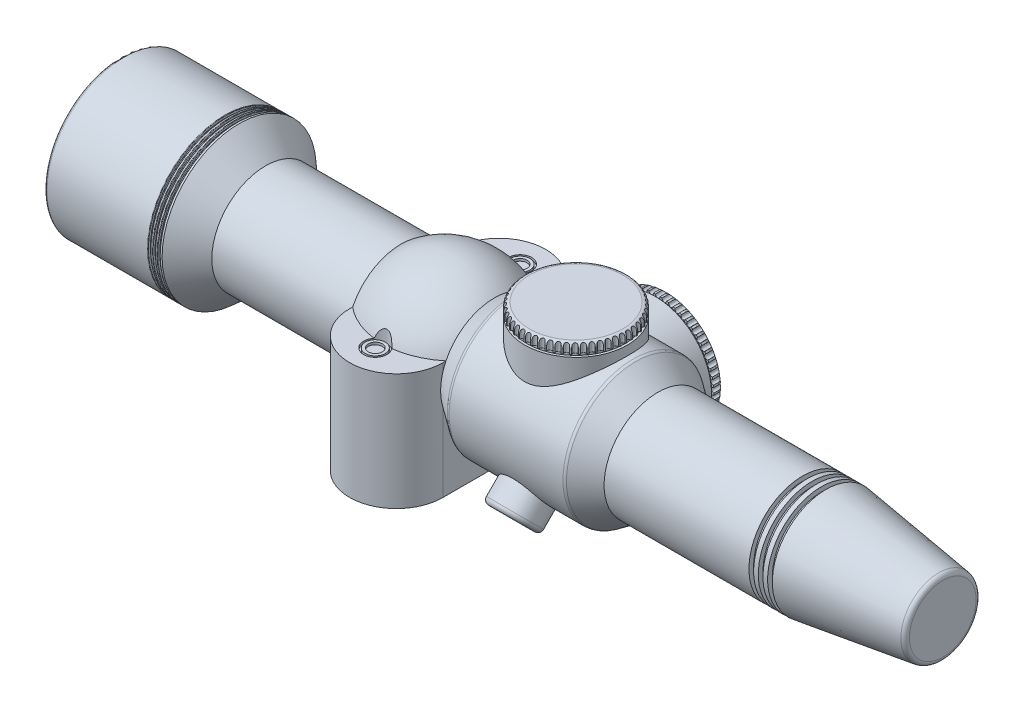
SolidWorks part; units mm, degrees
ref_plane "Front Plane" through (0, 0, 0) normal (0, 0, 1) x (1, 0, 0)
ref_plane "Top Plane" through (0, 0, 0) normal (0, 1, 0) x (1, 0, 0)
ref_plane "Right Plane" through (0, 0, 0) normal (1, 0, 0) x (0, 0, -1)
sketch "Sketch1" plane through (0, 0, 0) normal (1, 0, 0) x (0, 0, -1)
  circle A0 centre (0, 0) radius 16.5
  dimension "D1" = 33
extrude "Boss-Extrude1" add sketch "Sketch1" along normal blind 25.15
sketch "Sketch2" plane through (0, 0, 0) normal (-1, 0, 0) x (0, 0, 1)
  circle A0 centre (0, 0) radius 14.125
  dimension "D1" = 28.25
extrude "Cut-Extrude1" cut sketch "Sketch2" against normal blind 1
sketch "Sketch3" plane through (1, 0, 0) normal (-1, 0, 0) x (0, 0, 1)
  circle A0 centre (0, 0) radius 13.125
  dimension "D1" = 26.25
ref_plane "Plane1" through (25.15, 0, 0) normal (0, -1, 0) x (0, 0, 1)
extrude "Cut-Extrude6" cut sketch "Sketch3" against normal blind 1 contours A0
sketch "Sketch14" plane through (2, 0, 0) normal (-1, 0, 0) x (0, 0, 1)
  circle A0 centre (0, 0) radius 12.125
  dimension "D1" = 24.25
extrude "Cut-Extrude7" cut sketch "Sketch14" against normal blind 1
sketch "Sketch15" plane through (3, 0, 0) normal (-1, 0, 0) x (0, 0, 1)
  circle A0 centre (0, 0) radius 11.125
  dimension "D1" = 22.25
extrude "Cut-Extrude8" cut sketch "Sketch15" against normal blind 1
sketch "Sketch16" plane through (4, 0, 0) normal (-1, 0, 0) x (0, 0, 1)
  circle A0 centre (0, 0) radius 10.125
  dimension "D1" = 20.25
extrude "Cut-Extrude9" cut sketch "Sketch16" against normal blind 1
sketch "Sketch17" plane through (5, 0, 0) normal (-1, 0, 0) x (0, 0, 1)
  circle A0 centre (0, 0) radius 9.125
  dimension "D1" = 18.25
extrude "Cut-Extrude10" cut sketch "Sketch17" against normal blind 3
sketch "Sketch18" plane through (0, 0, 0) normal (0, 1, 0) x (1, 0, 0)
  line L0 (25.15, 0) -> (0, 0) construction
  line L1 (6.4671, 0) -> (8, 0)
  line L2 (8, 9.125) -> (8, -9.125) construction
  line L3 (8, 0) -> (8, 9.125)
  spline S0 degree 2 poles (8, 9.125) (6.4671, 4.5625) (6.4671, 0) knots 0 0 0 0.5 0.5 0.5
revolve "Revolve1" add sketch "Sketch18" angle 360 about axis through (25.15, 0, 0) along (-1, 0, 0)
sketch "Sketch20" plane through (0, 0, 0) normal (0, 1, 0) x (1, 0, 0)
  line L0 (25.15, 0) -> (30.8, 0)
  line L1 (25.15, -16.5) -> (25.15, 16.5) construction
  line L2 (25.15, 0) -> (0, 0) construction
  line L3 (30.8, 0) -> (30.8, 11.5)
  line L4 (30.8, 11.5) -> (25.15, 16.5)
  line L5 (25.15, 16.5) -> (25.15, 0)
  line L6 (25.15, 0) -> (25.0816, -0.0545)
  dimension "D1" = 11.5
  dimension "D2" = 5.65
revolve "Revolve5" add sketch "Sketch20" angle 360 about L0 region at (27.8068, 0, -7.0744)
sketch "Sketch21" plane through (30.8, 0, 0) normal (1, 0, 0) x (0, 0, -1)
  circle A0 centre (0, 0) radius 11.5
extrude "Shaft" add sketch "Sketch21" along normal blind 120
sketch "Sketch25" plane through (0, 0, 0) normal (0, 1, 0) x (1, 0, 0)
  line L0 (23.15, 16.5) -> (23.65, 16.5)
  line L1 (25.15, 16.5) -> (0, 16.5) construction
  line L2 (24.65, 16.5) -> (24.65, 16)
  line L3 (24.65, 16) -> (24.15, 16)
  line L4 (24.15, 16) -> (24.15, 16.5)
  line L5 (25.15, 16.5) -> (0, 16.5) construction
  line L7 (25.15, 16.5) -> (0, 16.5) construction
  line L8 (23.65, 16.5) -> (23.65, 16)
  line L9 (23.65, 16) -> (23.15, 16)
  line L10 (23.15, 16) -> (23.15, 16.5)
  line L11 (25.15, 16.5) -> (0, 16.5) construction
  line L12 (24.15, 16.5) -> (24.65, 16.5)
  line L13 (25.15, 16.5) -> (0, 16.5) construction
  line L14 (22.65, 16.5) -> (22.65, 16)
  line L15 (22.65, 16) -> (22.15, 16)
  line L16 (22.15, 16) -> (22.15, 16.5)
  line L17 (25.15, 16.5) -> (0, 16.5) construction
  line L18 (22.15, 16.5) -> (22.65, 16.5)
  line L20 (23.65, 16.5) -> (23.6371, 16.4877)
  dimension "D1" = 0.5
  dimension "D2" = 0.5
  dimension "D3" = 0.5
  dimension "D4" = 0.5
  dimension "D5" = 0.5
  dimension "D6" = 0.5
  dimension "D8" = 0.5
  dimension "D9" = 0.5
revolve "Cut-Revolve13" cut sketch "Sketch25" angle 360 about axis through (25.15, 0, 0) along (-1, 0, 0)
fillet "Fillet1" radius 0.1 6 edges at (24.65, 0, -16.5) (24.15, 0, -16.5) (23.65, 0, -16.5) (23.15, 0, -16.5) (22.65, 0, -16.5) (22.15, 0, -16.5)
fillet "Fillet2" radius 0.5 1 edges at (0, 0, -16.5)
sketch "Sketch26" plane through (0, 0, 0) normal (0, 1, 0) x (1, 0, 0)
  line L0 (150.8, -11.5) -> (150.8, 0)
  line L1 (150.8, -11.5) -> (150.8, 11.5) construction
  line L2 (150.8, 0) -> (175.8, 0)
  line L3 (150.8, 0) -> (30.8, 0) construction
  line L4 (175.8, 0) -> (175.8, -7.1302)
  line L5 (174.9386, -8.1206) -> (150.8, -11.5)
  arc A0 (175.8, -7.1302) -> (174.9386, -8.1206) centre (174.8, -7.1302) cw
  point P12 (175.8, -8)
  dimension "D3" = 1
  dimension "D1" = 25
  dimension "D2" = 8
revolve "Revolve6" add sketch "Sketch26" angle 360 about axis through (150.8, 0, 0) along (-1, 0, 0)
sketch "Sketch27" plane through (0, 0, 0) normal (0, 1, 0) x (1, 0, 0)
  line L0 (147.8, -11.5) -> (147.8, -10.5)
  line L1 (150.8, -11.5) -> (149.8, -11.5)
  line L2 (150.8, -11.5) -> (150.8, -10.5)
  line L3 (150.8, -10.5) -> (149.8, -10.5)
  line L4 (149.8, -11.5) -> (149.8, -10.5)
  line L5 (148.8, -11.5) -> (147.8, -11.5)
  line L6 (148.8, -11.5) -> (148.8, -10.5)
  line L7 (148.8, -10.5) -> (147.8, -10.5)
  line L8 (145.8, -11.5) -> (145.8, -10.5)
  line L9 (146.8, -11.5) -> (145.8, -11.5)
  line L10 (146.8, -11.5) -> (146.8, -10.5)
  line L11 (146.8, -10.5) -> (145.8, -10.5)
  dimension "D1" = 1
  dimension "D2" = 1
  dimension "D3" = 3
revolve "Cut-Revolve14" cut sketch "Sketch27" angle 360 about axis through (150.8, 0, 0) along (-1, 0, 0)
sketch "Sketch28" plane through (0, 0, 0) normal (0, 1, 0) x (1, 0, 0)
  line L0 (145.8, 0) -> (30.8, 0) construction
  line L1 (59.8, 11) -> (59.8, -11)
  line L2 (79.8, -11) -> (79.8, 11)
  line L3 (30.8, 11.5) -> (30.8, -11.5) construction
  arc A0 (79.8, 11) -> (59.8, 11) centre (69.8, 11) ccw
  arc A1 (59.8, -11) -> (79.8, -11) centre (69.8, -11) ccw
  dimension "D1" = 20
  dimension "D2" = 20
  dimension "D3" = 22
  dimension "D4" = 11
  dimension "D5" = 29
extrude "Boss-Extrude2" add sketch "Sketch28" against normal blind 20 and the other way blind 5
sketch "Sketch29" plane through (0, -20, 0) normal (0, -1, 0) x (1, 0, 0)
  circle A0 centre (69.8, -11) radius 2.75
  circle A1 centre (69.8, 7) radius 2.75
  dimension "D1" = 5.5
  dimension "D3" = 5.5
  dimension "D2" = 18
extrude "Cut-Extrude11" cut sketch "Sketch29" against normal blind 10
sketch "Sketch30" plane through (0, 0, 0) normal (0, 1, 0) x (1, 0, 0)
  line L0 (69.8, 14.8562) -> (54.6498, 14.8562) construction
  line L2 (59.8125, 11.5) -> (79.7875, 11.5)
  arc A0 (59.8125, 11.5) -> (79.7875, 11.5) centre (69.8, -1.6827) cw
revolve "Revolve7" add sketch "Sketch30" angle 180 about axis through (150.8, 0, 0) along (-1, 0, 0) reverse direction yes
sketch "Sketch31" plane through (0, 5, 0) normal (0, 1, 0) x (1, 0, 0)
  circle A0 centre (69.8, 15.5) radius 2.5
  arc A1 (79.8, 11) -> (59.8, 11) centre (69.8, 11) ccw construction
  point P2 (69.8, 21)
  dimension "D1" = 5
  dimension "D2" = 5.5
extrude "Cut-Extrude12" cut sketch "Sketch31" against normal blind 0.5 and the other way blind 10
sketch "Sketch32" plane through (0, 4.5, 0) normal (0, 1, 0) x (1, 0, 0)
  circle A0 centre (69.8, 15.5) radius 2.125
  circle A1 centre (69.8, 15.5) radius 1.5
  dimension "D1" = 4.25
  dimension "D2" = 3
extrude "Boss-Extrude3" add sketch "Sketch32" along normal blind 0.5
mirror "Mirror2" about plane through (0, 0, 0) normal (0, 0, 1) of "Boss-Extrude3", "Cut-Extrude12"
sketch "Sketch33" plane through (0, 0, 0) normal (0, 1, 0) x (1, 0, 0)
  line L0 (79.7875, 11.5) -> (84.5293, 14.8192)
  line L1 (85.1027, 15) -> (109.4723, 15)
  line L2 (110.0457, 14.8192) -> (114.7875, 11.5)
  line L3 (145.8, 11.5) -> (79.7875, 11.5) construction
  line L4 (114.7875, 11.5) -> (79.7875, 11.5)
  line L5 (145.8, 0) -> (79.7875, 0) construction
  arc A0 (110.0457, 14.8192) -> (109.4723, 15) centre (109.4723, 14) ccw
  arc A1 (85.1027, 15) -> (84.5293, 14.8192) centre (85.1027, 14) ccw
  point P11 (109.7875, 15)
  point P14 (84.7875, 15)
  dimension "D5" = 1
  dimension "D1" = 5
  dimension "D2" = 5
  dimension "D3" = 25
  dimension "D4" = 15
revolve "Revolve8" add sketch "Sketch33" angle 360 about axis through (150.8, 0, 0) along (-1, 0, 0)
sketch "Sketch34" plane through (0, 0, 0) normal (0, 0, 1) x (1, 0, 0)
  line L0 (85.1027, 0) -> (109.4723, 0) construction
  line L1 (114.7875, 11.5) -> (114.7875, -11.5) construction
  circle A0 centre (97.2875, 0) radius 12
  dimension "D2" = 24
  dimension "D1" = 17.5
extrude "Boss-Extrude4" add sketch "Sketch34" against normal blind 19.5
fillet "Fillet3" radius 1 1 edges at (109.2875, 0, -19.5)
sketch "Sketch36" plane through (0, 0, 0) normal (0, 1, 0) x (1, 0, 0)
  line L1 (85.2875, 18.5) -> (85.2875, 15) construction
  line L2 (85.2875, 17.5) -> (85.7875, 17.5)
  line L3 (85.2875, 17.5) -> (85.2875, 17)
  line L4 (85.2875, 17) -> (85.7875, 17)
  line L6 (85.7875, 17.5) -> (85.7875, 17)
  line L7 (109.2875, 18.5) -> (85.2875, 18.5) construction
  dimension "D1" = 0.5
  dimension "D2" = 0.5
  dimension "D3" = 1
revolve "Cut-Revolve15" cut sketch "Sketch36" angle 360 about axis through (97.2875, 0, -19.5) along (0, 0, 1)
sketch "Sketch38" plane through (0, 0, -19.5) normal (0, 0, -1) x (-1, 0, 0)
  line L0 (-97.2875, 0) -> (-97.2875, 15.7443) construction
sketch "Sketch39" plane through (0, 0, -19.5) normal (0, 0, -1) x (-1, 0, 0)
  line L0 (-97.2875, 0) -> (-97.2875, 15.7443) construction
  circle A0 centre (-97.2875, 12) radius 0.5
  circle A1 centre (-97.2875, 0) radius 12 construction
  dimension "D1" = 1
extrude "Cut-Extrude13" cut sketch "Sketch39" against normal up to next
pattern_circular "CirPattern1" count 53 over 360 about axis through (97.2875, 0, -18.5) along (0, 0, 1) of "Cut-Extrude13"
sketch "Sketch40" plane through (0, 0, 0) normal (0, 1, 0) x (1, 0, 0)
  line L0 (85.1027, 0) -> (109.4723, 0) construction
  line L1 (97.2875, 17) -> (97.2875, 14.9999) construction
  circle A0 centre (97.2875, 0) radius 11
  dimension "D1" = 22
extrude "Boss-Extrude5" add sketch "Sketch40" along normal blind 19.5
ref_plane "Plane3" through (0, 0, 0) normal (0, 0.7071, -0.7071) x (-1, 0, 0)
sketch "Sketch41" plane through (0, 0, 0) normal (0, 0.7071, -0.7071) x (-1, 0, 0)
  line L0 (-85.1027, 0) -> (-109.4723, 0) construction
  circle A0 centre (-97.2875, 0) radius 5
  dimension "D1" = 10
extrude "Boss-Extrude6" add sketch "Sketch41" against normal blind 19.5
fillet "Fillet4" radius 1 1 edges at (97.2875, -10.253, 17.3241)
sketch "Sketch43" plane through (0, 0, 0) normal (0, 0, 1) x (1, 0, 0)
  line L0 (108.2875, 15) -> (108.2875, 19.5) construction
  line L1 (108.2875, 17.5) -> (107.7875, 17.5)
  line L2 (108.2875, 17.5) -> (108.2875, 17)
  line L3 (108.2875, 17) -> (107.7875, 17)
  line L4 (107.7875, 17.5) -> (107.7875, 17)
  line L5 (108.2875, 19.5) -> (86.2875, 19.5) construction
  dimension "D1" = 0.5
  dimension "D2" = 0.5
  dimension "D3" = 2
revolve "Cut-Revolve16" cut sketch "Sketch43" angle 360 about axis through (97.2875, 19.5, 0) along (0, -1, 0)
fillet "Fillet5" radius 1 1 edges at (97.2875, 19.5, 11)
sketch "Sketch44" plane through (0, 19.5, 0) normal (0, 1, 0) x (1, 0, 0)
  circle A0 centre (97.2875, 11) radius 0.5
  arc A1 (101.7596, 10.0499) -> (92.8154, 10.0499) centre (97.2875, 0) ccw construction
  dimension "D1" = 1
extrude "Cut-Extrude14" cut sketch "Sketch44" against normal up to next
pattern_circular "CirPattern2" count 53 over 360 about axis through (97.2875, 18.5, 0) along (0, -1, 0) of "Cut-Extrude14"
